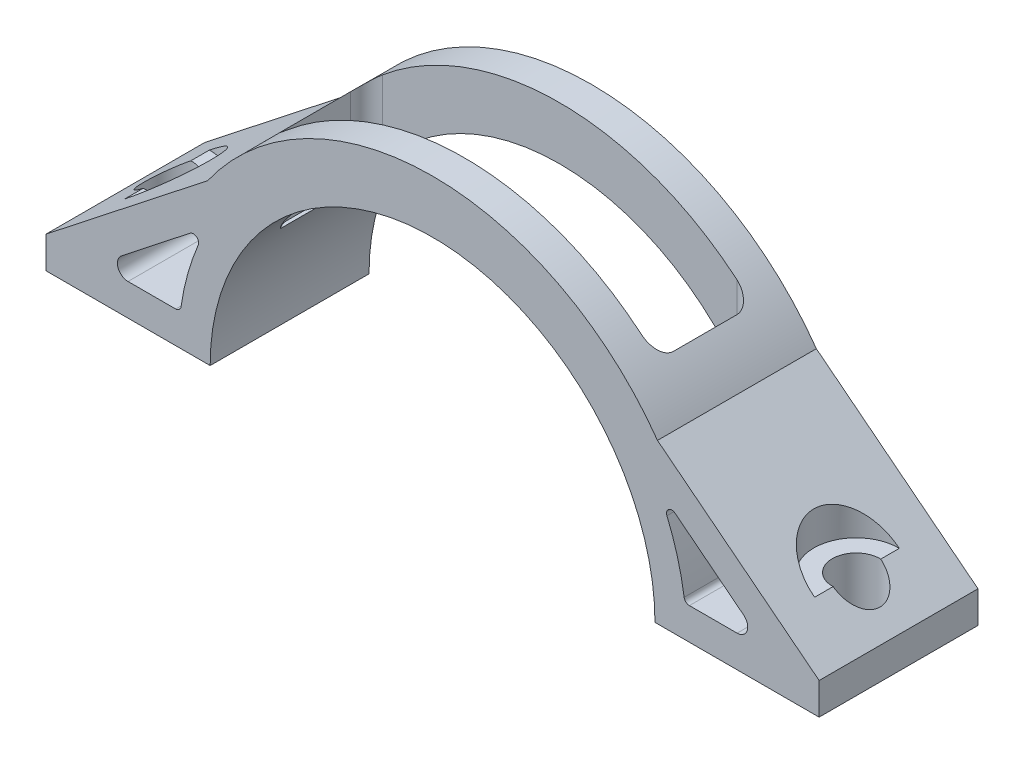
SolidWorks part; units mm, degrees
ref_plane "Alzado" through (0, 0, 0) normal (0, 0, 1) x (1, 0, 0)
ref_plane "Planta" through (0, 0, 0) normal (0, 1, 0) x (1, 0, 0)
ref_plane "Vista lateral" through (0, 0, 0) normal (1, 0, 0) x (0, 0, -1)
sketch "Croquis1" plane through (0, 0, 0) normal (0, 0, 1) x (1, 0, 0)
  line L0 (-26, 0) -> (-21, 0)
  line L5 (21, 0) -> (26, 0)
  arc A0 (26, 0) -> (-26, 0) centre (0, 0) ccw
  arc A2 (21, 0) -> (-21, 0) centre (0, 0) ccw
  point P0 (0, 0)
  dimension "D3" = 21
  dimension "D2" = 26
  dimension "D1" = 52
extrude "Saliente-Extruir1" add sketch "Croquis1" along normal mid plane 15
sketch "Croquis2" plane through (0, 0, 0) normal (0, 0, 1) x (1, 0, 0)
  line L0 (26, 0) -> (36.5, 0)
  line L1 (36.5, 0) -> (36.5, 3)
  line L2 (36.5, 3) -> (21.2368, 15)
  arc A0 (26, 0) -> (-26, 0) centre (0, 0) ccw construction
  arc A1 (26, 0) -> (21.2368, 15) centre (0, 0) ccw
  dimension "D1" = 10.5
  dimension "D2" = 3
  dimension "D3" = 15
extrude "Saliente-Extruir2" add sketch "Croquis2" along normal mid plane 15
sketch "Croquis3" plane through (0, 0, 0) normal (0, -1, 0) x (1, 0, 0)
  line L0 (21, -7.5) -> (36.5, -7.5) construction
  line L1 (36.5, 7.5) -> (36.5, -7.5) construction
  circle A0 centre (32.5, 0) radius 2.25
  dimension "D3" = 4.5
  dimension "D1" = 7.5
  dimension "D2" = 4
extrude "Cortar-Extruir1" cut sketch "Croquis3" against normal through all
ref_plane "Plano1" through (0, 6.09, 0) normal (0, -1, 0) x (-1, 0, 0)
sketch "Croquis4" plane through (0, 6.09, 0) normal (0, -1, 0) x (-1, 0, 0)
  circle A0 centre (-32.5, 0) radius 4
  dimension "D1" = 8
extrude "Cortar-Extruir2" cut sketch "Croquis4" against normal through all
mirror "Simetría1" about plane through (0, 0, 0) normal (1, 0, 0) of "Cortar-Extruir2", "Saliente-Extruir2", "Cortar-Extruir1"
sketch "Croquis6" plane through (0, 0, 7.5) normal (0, 0, 1) x (1, 0, 0)
  line L5 (33.5, 0) -> (33.5, 1.5425)
  line L6 (33.5, 1.5425) -> (19.3826, 12.6416)
  line L8 (29.3742, 4.7861) -> (22.8989, 9.877)
  line L10 (23.8118, 3) -> (36.5, 3)
  line L11 (24.2487, 3) -> (28.7562, 3)
  arc A1 (23.7538, 3.4286) -> (24.2487, 3) centre (24.2487, 3.5) ccw
  arc A2 (23.8118, 3) -> (-24, 0) centre (0, 0) ccw
  arc A3 (23.7538, 3.4286) -> (22.1289, 9.2904) centre (0, 0) ccw
  arc A4 (22.1289, 9.2904) -> (22.8989, 9.877) centre (22.5899, 9.484) cw
  arc A5 (28.7562, 3) -> (29.3742, 4.7861) centre (28.7562, 4) ccw
  dimension "D3" = 0.5
  dimension "D4" = 1
  dimension "D1" = 3
  dimension "D2" = 3
extrude "Cortar-Extruir3" cut sketch "Croquis6" against normal through all
mirror "Simetría2" about plane through (0, 0, 0) normal (0, 0, 1) of "Cortar-Extruir3"
ref_plane "Plano2" through (0, 26, 0) normal (0, 1, 0) x (1, 0, 0)
sketch "Croquis8" plane through (0, 26, 0) normal (0, 1, 0) x (1, 0, 0)
  line L17 (-18.2368, -4.5) -> (18.2368, -4.5)
  line L18 (18.2368, -4.5) -> (18.2368, 4.5)
  line L19 (-18.2368, 4.5) -> (-18.2368, -4.5)
  line L20 (18.2368, 4.5) -> (-18.2368, 4.5)
  line L21 (-16.7368, -4.5) -> (16.7368, -4.5)
  line L22 (18.2368, -3) -> (18.2368, 3)
  line L23 (-18.2368, 3) -> (-18.2368, -3)
  line L24 (16.7368, 4.5) -> (-16.7368, 4.5)
  arc A0 (-16.7368, -4.5) -> (-18.2368, -3) centre (-16.7368, -3) cw
  arc A1 (-18.2368, 3) -> (-16.7368, 4.5) centre (-16.7368, 3) cw
  arc A2 (18.2368, 3) -> (16.7368, 4.5) centre (16.7368, 3) ccw
  arc A3 (16.7368, -4.5) -> (18.2368, -3) centre (16.7368, -3) ccw
  dimension "D2" = 1.5
  dimension "D1" = 3
extrude "Cortar-Extruir4" cut sketch "Croquis8" against normal blind 15
mirror "Simetría3" about plane through (0, 0, 0) normal (1, 0, 0) of "Cortar-Extruir3", "Simetría2"
